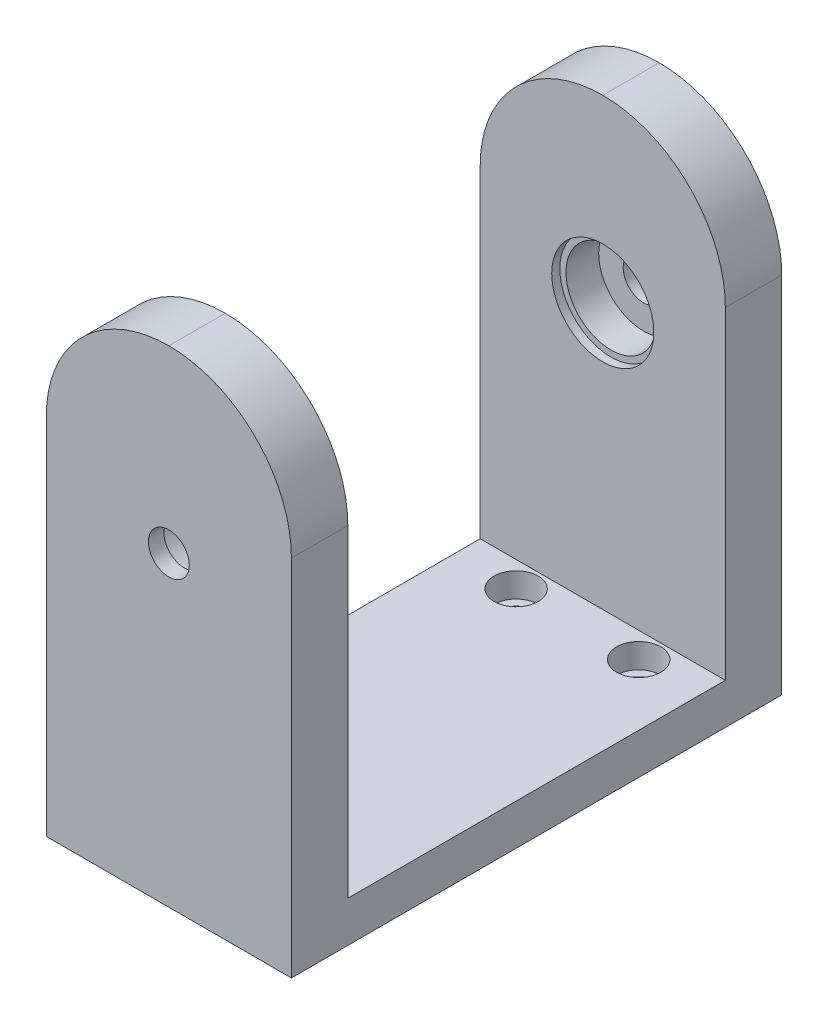
SolidWorks part; units mm, degrees
ref_plane "Front Plane" through (0, 0, 0) normal (0, 0, 1) x (1, 0, 0)
ref_plane "Top Plane" through (0, 0, 0) normal (0, 1, 0) x (1, 0, 0)
ref_plane "Right Plane" through (0, 0, 0) normal (1, 0, 0) x (0, 0, -1)
sketch "Sketch1" plane through (0, 0, 0) normal (0, 1, 0) x (1, 0, 0)
  line L0 (-1.3042, 0) -> (2.0884, 0) construction
  line L1 (0, 5.5134) -> (0, -5.3226) construction
  line L2 (15, 20) -> (-15, 20) construction
  line L3 (15, -30) -> (-15, -30)
  line L4 (15, -30) -> (15, 30)
  line L5 (15, 30) -> (-15, 30)
  line L6 (-15, -30) -> (-15, 30)
  line L7 (15, -30) -> (-15, 30) construction
  line L8 (15, 30) -> (-15, -30) construction
  line L9 (15, -20) -> (-15, -20) construction
  circle A0 centre (-7.5, 20) radius 1.65
  circle A1 centre (7.5, 20) radius 1.65
  circle A2 centre (7.5, -20) radius 1.65
  circle A3 centre (-7.5, -20) radius 1.65
  point P4 (0, 0)
  dimension "D4" = 3.3
  dimension "D1" = 10
  dimension "D2" = 40
  dimension "D3" = 30
  dimension "D5" = 15
extrude "Boss-Extrude1" add sketch "Sketch1" along normal blind 5
sketch "Sketch7" plane through (0, 5, 0) normal (0, 1, 0) x (1, 0, 0)
  circle A0 centre (-7.5, 20) radius 2.7
  circle A1 centre (7.5, 20) radius 2.7
  circle A2 centre (-7.5, -20) radius 2.7
  circle A3 centre (7.5, -20) radius 2.7
  dimension "D1" = 5.4
extrude "Cut-Extrude3" cut sketch "Sketch7" against normal blind 3
ref_plane "Plane1" through (0, 0, 30) normal (0, 0, 1) x (1, 0, 0)
sketch "Sketch3" plane through (0, 0, 30) normal (0, 0, 1) x (1, 0, 0)
  line L0 (-15, 5) -> (15, 5)
  line L1 (15, 5) -> (15, 0) construction
  line L2 (-15, 5) -> (15, 5) construction
  line L3 (15, 5) -> (15, 37.5)
  line L4 (-15, 5) -> (-15, 37.5)
  line L5 (-15, 37.5) -> (-15, 59.5)
  line L6 (15, 37.5) -> (15, 59.5)
  line L7 (15, 59.5) -> (-15, 59.5)
  circle A1 centre (0, 37.5) radius 2.5
  circle A2 centre (0, 37.5) radius 22.5 construction
  dimension "D1" = 5
  dimension "D3" = 45
  dimension "D2" = 37.5
  dimension "D4" = 22
extrude "Boss-Extrude2" add sketch "Sketch3" against normal blind 6.9
sketch "Sketch4" plane through (0, 0, 23.1) normal (0, 0, -1) x (-1, 0, 0)
  circle A0 centre (0, 37.5) radius 6.25
  dimension "D1" = 12.5
extrude "Cut-Extrude1" cut sketch "Sketch4" against normal blind 1
sketch "Sketch6" plane through (0, 0, 24.1) normal (0, 0, -1) x (-1, 0, 0)
  circle A0 centre (0, 37.5) radius 5.5
  dimension "D1" = 11
extrude "Cut-Extrude2" cut sketch "Sketch6" against normal blind 4
mirror "Mirror2" about plane through (0, 0, 0) normal (0, 0, 1) of "Cut-Extrude2", "Cut-Extrude1", "Boss-Extrude2"
fillet "Fillet1" radius 15 4 edges at (15, 59.5, -26.55) (-15, 59.5, -26.55) (-15, 59.5, 26.55) (15, 59.5, 26.55)
